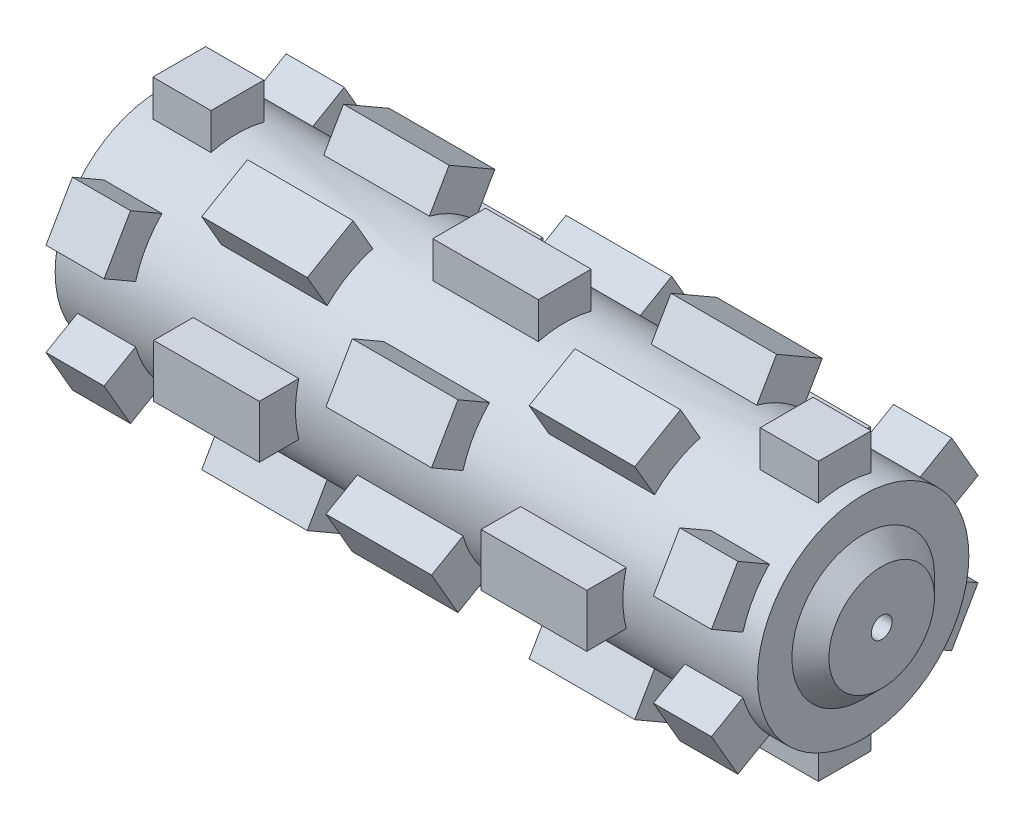
SolidWorks part; units mm, degrees
material "AISI 304"
ref_plane "Front Plane" through (0, 0, 0) normal (0, 0, 1) x (1, 0, 0)
ref_plane "Top Plane" through (0, 0, 0) normal (0, 1, 0) x (1, 0, 0)
ref_plane "Right Plane" through (0, 0, 0) normal (1, 0, 0) x (0, 0, -1)
sketch "Sketch1" plane through (0, 0, 0) normal (1, 0, 0) x (0, 0, -1)
  line L0 (0, -34.925) -> (0, 34.925) construction
  line L1 (-12.7, 66.675) -> (12.7, 66.675)
  line L2 (-12.7, 66.675) -> (-12.7, 34.925)
  line L3 (-12.7, 34.925) -> (12.7, 34.925)
  line L4 (12.7, 66.675) -> (12.7, 34.925)
  line L5 (-12.7, 66.675) -> (12.7, 34.925) construction
  line L6 (-12.7, 34.925) -> (12.7, 66.675) construction
  line L7 (51.3922, 44.336) -> (23.8959, 28.461)
  line L8 (51.3922, 44.336) -> (64.0922, 22.339)
  line L9 (64.0922, 22.339) -> (36.5959, 6.464)
  line L10 (23.8959, 28.461) -> (36.5959, 6.464)
  line L11 (64.0922, -22.339) -> (36.5959, -6.464)
  line L12 (64.0922, -22.339) -> (51.3922, -44.336)
  line L13 (51.3922, -44.336) -> (23.8959, -28.461)
  line L14 (36.5959, -6.464) -> (23.8959, -28.461)
  line L15 (12.7, -66.675) -> (12.7, -34.925)
  line L16 (12.7, -66.675) -> (-12.7, -66.675)
  line L17 (-12.7, -66.675) -> (-12.7, -34.925)
  line L18 (12.7, -34.925) -> (-12.7, -34.925)
  line L19 (-51.3922, -44.336) -> (-23.8959, -28.461)
  line L20 (-51.3922, -44.336) -> (-64.0922, -22.339)
  line L21 (-64.0922, -22.339) -> (-36.5959, -6.464)
  line L22 (-23.8959, -28.461) -> (-36.5959, -6.464)
  line L23 (-64.0922, 22.339) -> (-36.5959, 6.464)
  line L24 (-64.0922, 22.339) -> (-51.3922, 44.336)
  line L25 (-51.3922, 44.336) -> (-23.8959, 28.461)
  line L26 (-36.5959, 6.464) -> (-23.8959, 28.461)
  circle A0 centre (0, 0) radius 50.8
  point P3 (0, 50.8)
  point P10 (0, 0)
  point P14 (0, 0)
  point P34 (0, 0)
  dimension "D1" = 101.6
  dimension "D3" = 25.4
  dimension "D4" = 31.75
  dimension "D2" = 6
extrude "Boss-Extrude3" add sketch "Sketch1" along normal blind 50.8 contours A0 | L2 L1 L4 L3 | L23 L26 L25 L24 | L19 L22 L21 L20 | L15 L18 L17 L16 | L11 L14 L13 L12 | L7 L10 L9 L8
sketch "Sketch2" plane through (50.8, 0, 0) normal (1, 0, 0) x (0, 0, -1)
  circle A0 centre (0, 0) radius 50.8
extrude "Boss-Extrude4" add sketch "Sketch2" along normal blind 27.94
sketch "Sketch3" plane through (78.74, 0, 0) normal (1, 0, 0) x (0, 0, -1)
  line L0 (0, 0) -> (12.7, 66.675) construction
  line L1 (12.7, 66.675) -> (12.7, 49.1869) construction
  line L2 (36.4373, 12.7) -> (36.4373, 0)
  line L3 (51.3922, 44.336) -> (0, 0) construction
  line L4 (34.0936, 59.0519) -> (0, 0) construction
  line L5 (18.2186, 31.5556) -> (29.2172, 25.2056)
  line L6 (29.2172, 25.2056) -> (45.0922, 52.7019)
  line L7 (45.0922, 52.7019) -> (23.0951, 65.4019)
  line L8 (23.0951, 65.4019) -> (7.2201, 37.9056)
  line L9 (7.2201, 37.9056) -> (18.2186, 31.5556)
  line L10 (36.4373, 0) -> (36.4373, -12.7)
  line L11 (36.4373, -12.7) -> (68.1873, -12.7)
  line L12 (68.1873, -12.7) -> (68.1873, 12.7)
  line L13 (68.1873, 12.7) -> (36.4373, 12.7)
  line L14 (29.2172, -25.2056) -> (18.2186, -31.5556)
  line L15 (18.2186, -31.5556) -> (7.2201, -37.9056)
  line L16 (7.2201, -37.9056) -> (23.0951, -65.4019)
  line L17 (23.0951, -65.4019) -> (45.0922, -52.7019)
  line L18 (45.0922, -52.7019) -> (29.2172, -25.2056)
  line L19 (-7.2201, -37.9056) -> (-18.2186, -31.5556)
  line L20 (-18.2186, -31.5556) -> (-29.2172, -25.2056)
  line L21 (-29.2172, -25.2056) -> (-45.0922, -52.7019)
  line L22 (-45.0922, -52.7019) -> (-23.0951, -65.4019)
  line L23 (-23.0951, -65.4019) -> (-7.2201, -37.9056)
  line L24 (-36.4373, -12.7) -> (-36.4373, 0)
  line L25 (-36.4373, 0) -> (-36.4373, 12.7)
  line L26 (-36.4373, 12.7) -> (-68.1873, 12.7)
  line L27 (-68.1873, 12.7) -> (-68.1873, -12.7)
  line L28 (-68.1873, -12.7) -> (-36.4373, -12.7)
  line L29 (-29.2172, 25.2056) -> (-18.2186, 31.5556)
  line L30 (-18.2186, 31.5556) -> (-7.2201, 37.9056)
  line L31 (-7.2201, 37.9056) -> (-23.0951, 65.4019)
  line L32 (-23.0951, 65.4019) -> (-45.0922, 52.7019)
  line L33 (-45.0922, 52.7019) -> (-29.2172, 25.2056)
  circle A0 centre (0, 0) radius 50.8
  circle A1 centre (0, 0) radius 67.8737 construction
  point P44 (0, 0)
  dimension "D1" = 31.75
  dimension "D2" = 25.4
  dimension "D3" = 6
extrude "Boss-Extrude5" add sketch "Sketch3" along normal blind 50.8 contours A0 | L24 L25 L26 L27 L28 | L29 L30 L31 L32 L33 | L9 L5 L6 L7 L8 | L2 L10 L11 L12 L13 | L14 L15 L16 L17 L18 | L19 L20 L21 L22 L23
sketch "Sketch4" plane through (129.54, 0, 0) normal (1, 0, 0) x (0, 0, -1)
  circle A0 centre (0, 0) radius 50.8
extrude "Boss-Extrude6" add sketch "Sketch4" along normal blind 27.94
sketch "Sketch5" plane through (157.48, 0, 0) normal (1, 0, 0) x (0, 0, -1)
  line L0 (12.7, 66.675) -> (12.7, 49.1869) construction
  line L1 (-12.7, 66.675) -> (12.7, 66.675)
  line L2 (-12.7, 66.675) -> (-12.7, 34.925)
  line L3 (-12.7, 34.925) -> (12.7, 34.925)
  line L4 (12.7, 66.675) -> (12.7, 34.925)
  line L5 (51.3922, 44.336) -> (23.8959, 28.461)
  line L6 (51.3922, 44.336) -> (64.0922, 22.339)
  line L7 (64.0922, 22.339) -> (36.5959, 6.464)
  line L8 (23.8959, 28.461) -> (36.5959, 6.464)
  line L9 (64.0922, -22.339) -> (36.5959, -6.464)
  line L10 (64.0922, -22.339) -> (51.3922, -44.336)
  line L11 (51.3922, -44.336) -> (23.8959, -28.461)
  line L12 (36.5959, -6.464) -> (23.8959, -28.461)
  line L13 (12.7, -66.675) -> (12.7, -34.925)
  line L14 (12.7, -66.675) -> (-12.7, -66.675)
  line L15 (-12.7, -66.675) -> (-12.7, -34.925)
  line L16 (12.7, -34.925) -> (-12.7, -34.925)
  line L17 (-51.3922, -44.336) -> (-23.8959, -28.461)
  line L18 (-51.3922, -44.336) -> (-64.0922, -22.339)
  line L19 (-64.0922, -22.339) -> (-36.5959, -6.464)
  line L20 (-23.8959, -28.461) -> (-36.5959, -6.464)
  line L21 (-64.0922, 22.339) -> (-36.5959, 6.464)
  line L22 (-64.0922, 22.339) -> (-51.3922, 44.336)
  line L23 (-51.3922, 44.336) -> (-23.8959, 28.461)
  line L24 (-36.5959, 6.464) -> (-23.8959, 28.461)
  circle A0 centre (0, 0) radius 50.8
  point P33 (0, 0)
  dimension "D1" = 31.75
  dimension "D2" = 25.4
  dimension "D3" = 6
extrude "Boss-Extrude7" add sketch "Sketch5" along normal blind 27.94 contours A0 | L21 L24 L23 L22 | L2 L1 L4 L3 | L5 L8 L7 L6 | L17 L20 L19 L18 | L13 L16 L15 L14 | L9 L12 L11 L10
sketch "Sketch6" plane through (0, 0, 0) normal (-1, 0, 0) x (0, 0, 1)
  circle A0 centre (0, 0) radius 50.8
extrude "Boss-Extrude8" add sketch "Sketch6" along normal blind 27.94
sketch "Sketch7" plane through (-27.94, 0, 0) normal (-1, 0, 0) x (0, 0, 1)
  line L0 (23.0951, 65.4019) -> (45.0922, 52.7019)
  line L1 (45.0922, 52.7019) -> (29.2172, 25.2056)
  line L2 (29.2172, 25.2056) -> (7.2201, 37.9056)
  line L3 (7.2201, 37.9056) -> (23.0951, 65.4019)
  line L4 (36.4373, 12.7) -> (68.1873, 12.7)
  line L5 (68.1873, 12.7) -> (68.1873, -12.7)
  line L6 (68.1873, -12.7) -> (36.4373, -12.7)
  line L7 (36.4373, -12.7) -> (36.4373, 12.7)
  line L8 (29.2172, -25.2056) -> (45.0922, -52.7019)
  line L9 (45.0922, -52.7019) -> (23.0951, -65.4019)
  line L10 (23.0951, -65.4019) -> (7.2201, -37.9056)
  line L11 (7.2201, -37.9056) -> (29.2172, -25.2056)
  line L12 (-7.2201, -37.9056) -> (-23.0951, -65.4019)
  line L13 (-23.0951, -65.4019) -> (-45.0922, -52.7019)
  line L14 (-45.0922, -52.7019) -> (-29.2172, -25.2056)
  line L15 (-29.2172, -25.2056) -> (-7.2201, -37.9056)
  line L16 (-36.4373, -12.7) -> (-68.1873, -12.7)
  line L17 (-68.1873, -12.7) -> (-68.1873, 12.7)
  line L18 (-68.1873, 12.7) -> (-36.4373, 12.7)
  line L19 (-36.4373, 12.7) -> (-36.4373, -12.7)
  line L20 (-29.2172, 25.2056) -> (-45.0922, 52.7019)
  line L21 (-45.0922, 52.7019) -> (-23.0951, 65.4019)
  line L22 (-23.0951, 65.4019) -> (-7.2201, 37.9056)
  line L23 (-7.2201, 37.9056) -> (-29.2172, 25.2056)
  circle A0 centre (0, 0) radius 50.8
  point P28 (0, 0)
  dimension "D1" = 25.4
  dimension "D2" = 31.75
  dimension "D3" = 6
extrude "Boss-Extrude9" add sketch "Sketch7" along normal blind 50.8 contours L3 L0 L1 L2 | L20 L21 L22 L23 | A0 | L16 L17 L18 L19 | L12 L13 L14 L15 | L8 L9 L10 L11 | L4 L5 L6 L7
sketch "Sketch8" plane through (-78.74, 0, 0) normal (-1, 0, 0) x (0, 0, 1)
  circle A0 centre (0, 0) radius 50.8
extrude "Boss-Extrude10" add sketch "Sketch8" along normal blind 27.94
sketch "Sketch9" plane through (-106.68, 0, 0) normal (-1, 0, 0) x (0, 0, 1)
  line L0 (12.7, 66.675) -> (12.7, 49.1869) construction
  line L1 (-12.7, 66.675) -> (12.7, 66.675)
  line L2 (-12.7, 66.675) -> (-12.7, 34.925)
  line L3 (-12.7, 34.925) -> (12.7, 34.925)
  line L4 (12.7, 66.675) -> (12.7, 34.925)
  line L5 (51.3922, 44.336) -> (23.8959, 28.461)
  line L6 (51.3922, 44.336) -> (64.0922, 22.339)
  line L7 (64.0922, 22.339) -> (36.5959, 6.464)
  line L8 (23.8959, 28.461) -> (36.5959, 6.464)
  line L9 (64.0922, -22.339) -> (36.5959, -6.464)
  line L10 (64.0922, -22.339) -> (51.3922, -44.336)
  line L11 (51.3922, -44.336) -> (23.8959, -28.461)
  line L12 (36.5959, -6.464) -> (23.8959, -28.461)
  line L13 (12.7, -66.675) -> (12.7, -34.925)
  line L14 (12.7, -66.675) -> (-12.7, -66.675)
  line L15 (-12.7, -66.675) -> (-12.7, -34.925)
  line L16 (12.7, -34.925) -> (-12.7, -34.925)
  line L17 (-51.3922, -44.336) -> (-23.8959, -28.461)
  line L18 (-51.3922, -44.336) -> (-64.0922, -22.339)
  line L19 (-64.0922, -22.339) -> (-36.5959, -6.464)
  line L20 (-23.8959, -28.461) -> (-36.5959, -6.464)
  line L21 (-64.0922, 22.339) -> (-36.5959, 6.464)
  line L22 (-64.0922, 22.339) -> (-51.3922, 44.336)
  line L23 (-51.3922, 44.336) -> (-23.8959, 28.461)
  line L24 (-36.5959, 6.464) -> (-23.8959, 28.461)
  circle A0 centre (0, 0) radius 50.8
  point P33 (0, 0)
  dimension "D1" = 31.75
  dimension "D2" = 25.4
  dimension "D3" = 6
extrude "Boss-Extrude11" add sketch "Sketch9" along normal blind 27.94 contours A0 | L21 L24 L23 L22 | L17 L20 L19 L18 | L13 L16 L15 L14 | L9 L12 L11 L10 | L5 L8 L7 L6 | L2 L1 L4 L3
sketch "Sketch10" plane through (185.42, 0, 0) normal (1, 0, 0) x (0, 0, -1)
  circle A0 centre (0, 0) radius 50.8
extrude "Boss-Extrude12" add sketch "Sketch10" along normal blind 8.89
sketch "Sketch11" plane through (-134.62, 0, 0) normal (-1, 0, 0) x (0, 0, 1)
  circle A0 centre (0, 0) radius 50.8
extrude "Boss-Extrude13" add sketch "Sketch11" along normal blind 8.89
sketch "Sketch12" plane through (194.31, 0, 0) normal (1, 0, 0) x (0, 0, -1)
  circle A1 centre (0, 0) radius 25.4
  dimension "D2" = 50.8
extrude "Boss-Extrude14" add sketch "Sketch12" along normal blind 8.89
sketch "Sketch13" plane through (-143.51, 0, 0) normal (-1, 0, 0) x (0, 0, 1)
  circle A0 centre (0, 0) radius 25.4
  dimension "D1" = 50.8
extrude "Boss-Extrude15" add sketch "Sketch13" along normal blind 8.89
sketch "Sketch14" plane through (-152.4, 0, 0) normal (-1, 0, 0) x (0, 0, 1)
  circle A0 centre (0, 0) radius 5
  dimension "D1" = 10
extrude "Cut-Extrude1" cut sketch "Sketch14" against normal through all
chamfer "Chamfer3" distance 8.89 angle 45 2 edges at (-143.51, 0, 25.4) (194.31, 0, -25.4)
